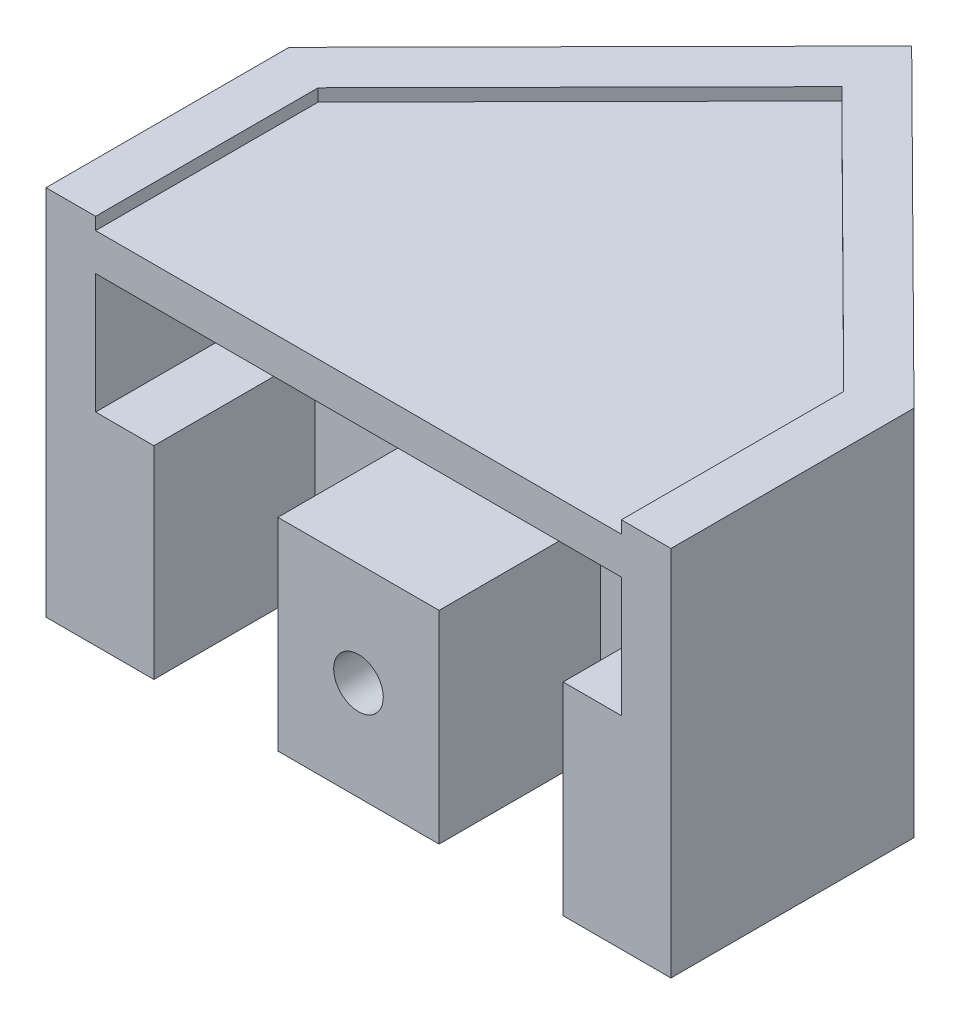
SolidWorks part; units mm, degrees
ref_plane "Plan de face" through (0, 0, 0) normal (0, 0, 1) x (1, 0, 0)
ref_plane "Plan de dessus" through (0, 0, 0) normal (0, 1, 0) x (1, 0, 0)
ref_plane "Plan de droite" through (0, 0, 0) normal (1, 0, 0) x (0, 0, -1)
sketch "Sketch2" plane through (0, 0, 0) normal (0, 0, 1) x (1, 0, 0)
  line L1 (0, 0) -> (-25.2, 0)
  line L2 (0, 0) -> (0, 15)
  line L3 (0, 15) -> (-25.2, 15)
  line L4 (-25.2, 0) -> (-25.2, 15)
  dimension "D1" = 25.2
  dimension "D2" = 15
extrude "Boss-Extrude2" add sketch "Sketch2" along normal blind 2
sketch "Sketch3" plane through (0, 0, 2) normal (0, 0, 1) x (1, 0, 0)
  line L0 (0, 15) -> (-25.2, 15) construction
  line L1 (-25.2, 0) -> (-23.2, 0)
  line L2 (-25.2, 0) -> (-25.2, 15)
  line L3 (-25.2, 15) -> (-23.2, 15)
  line L4 (-23.2, 0) -> (-23.2, 15)
  line L6 (-23.2, 13) -> (0, 13)
  line L7 (-23.2, 13) -> (-23.2, 15)
  line L8 (-23.2, 15) -> (0, 15)
  line L9 (0, 13) -> (0, 15)
  line L10 (0, 0) -> (-2, 0)
  line L11 (0, 0) -> (0, 13)
  line L12 (0, 13) -> (-2, 13)
  line L13 (-2, 0) -> (-2, 13)
  line M4 (0, 0) -> (0, 15)
  line M5 (0, 15) -> (-25.2, 15)
  line M6 (-25.2, 15) -> (-25.2, 0)
  line M7 (-25.2, 0) -> (0, 0)
  dimension "D1" = 2
  dimension "D2" = 2
  dimension "D3" = 2
extrude "Boss-Extrude3" add sketch "Sketch3" along normal blind 7.8 contours L4 M7 M5 M6 | L4 L6 M4 M5 | L13 L6 M7 M4 region at (-24.2, 7.5, 2) region at (-11.6, 14, 2) region at (-1, 6.5, 2)
sketch "Sketch4" plane through (0, 15, 0) normal (0, 1, 0) x (1, 0, 0)
  line L0 (0, 0) -> (-12.6933, 12.5997) construction
  line L1 (-25.2, 0) -> (-12.6933, 12.5997) construction
  line L2 (0, 0) -> (-12.6933, 12.5997)
  line L3 (-12.6933, 12.5997) -> (-25.2, 0)
  line L4 (-25.2, 0) -> (0, 0)
  point P4 (-12.8999, 12.9691)
  point P6 (-12.2, 12.9581)
extrude "Boss-Extrude4" add sketch "Sketch4" against normal through all
sketch "Sketch5" plane through (0, 0, 2) normal (0, 0, 1) x (1, 0, 0)
  line L0 (-23.2, 0) -> (-2, 0) construction
  line L1 (-20.85, 0) -> (-4.35, 0)
  line L2 (-20.85, 0) -> (-20.85, 8.1631)
  line L3 (-20.85, 8.1631) -> (-4.35, 8.1631)
  line L4 (-4.35, 0) -> (-4.35, 8.1631)
  line L5 (-20.1, 6) -> (-20.1, 8.5) construction
  line L7 (-2, 0) -> (-2, 13) construction
  line L8 (-23.2, 0) -> (-2, 0)
  line L9 (-23.2, 0) -> (-23.2, 8.1631)
  line L10 (-23.2, 8.1631) -> (-2, 8.1631)
  line L11 (-2, 0) -> (-2, 8.1631)
  line L12 (-17.6, 6) -> (-17.6, 8.5) construction
  line L13 (-15.85, 0) -> (-9.35, 0)
  line L14 (-15.85, 0) -> (-15.85, 8.1631)
  line L15 (-15.85, 8.1631) -> (-9.35, 8.1631)
  line L16 (-9.35, 0) -> (-9.35, 8.1631)
  line M7 (-23.2, 0) -> (-2, 0)
  line M8 (-2, 0) -> (-2, 13)
  line M10 (-23.2, 13) -> (-23.2, 0)
  dimension "D1" = 16.5
  dimension "D2" = 0.75
  dimension "D3" = 0
  dimension "D4" = 6.5
  dimension "D5" = 1.75
extrude "Boss-Extrude5" add sketch "Sketch5" along normal blind 7.8 contours L8 L16 L10 L14 | L10 L4 M7 M8 | L10 L2 M10 M7 region at (-22.025, 4.0815, 2) region at (-12.6, 4.0815, 2) region at (-3.175, 4.0815, 2)
sketch "Sketch6" plane through (0, 0, 2) normal (0, 0, 1) x (1, 0, 0)
  line L1 (-20.85, 0) -> (-15.85, 0)
  line L2 (-20.85, 0) -> (-20.85, 8.1631)
  line L3 (-20.85, 8.1631) -> (-15.85, 8.1631)
  line L4 (-15.85, 0) -> (-15.85, 8.1631)
  line L5 (-9.35, 0) -> (-4.35, 0)
  line L6 (-9.35, 0) -> (-9.35, 8.1631)
  line L7 (-9.35, 8.1631) -> (-4.35, 8.1631)
  line L8 (-4.35, 0) -> (-4.35, 8.1631)
extrude "Boss-Extrude6" add sketch "Sketch6" along normal blind 1.3
sketch "Sketch8" plane through (0, 15, 0) normal (0, 1, 0) x (1, 0, 0)
  line L6 (-23.2, -7.8) -> (-2, -7.8)
  line L7 (-23.2, -7.8) -> (-23.2, -9.8)
  line L8 (-23.2, -9.8) -> (-2, -9.8)
  line L9 (-2, -7.8) -> (-2, -9.8)
  line L10 (-2, -7.8) -> (-2, -0.8328)
  line L11 (-2, -0.8328) -> (-12.6829, 9.7712)
  line L12 (-12.6829, 9.7712) -> (-23.2, -0.8241)
  line L13 (-23.2, -0.8241) -> (-23.2, -7.8)
  line L14 (-23.2, -7.8) -> (-2, -7.8)
  line L15 (-2, -7.8) -> (-2, -0.8328)
  line L16 (-2, -0.8328) -> (-12.6829, 9.7712)
  line L17 (-12.6829, 9.7712) -> (-23.2, -0.8241)
  line L18 (-23.2, -0.8241) -> (-23.2, -7.8)
  line L19 (-23.2, -7.8) -> (-2, -7.8)
  line M10 (-25.2, -9.8) -> (0, -9.8)
  dimension "D1" = 2
extrude "Cut-Extrude1" cut sketch "Sketch8" against normal blind 0.5 contours L17 L18 L6 L15 L16 | L9 L6 L7 M10 region at (-12.6132, 15, 1.2828) region at (-12.6, 15, 8.8)
sketch "Sketch10" plane through (0, 0, 9.8) normal (0, 0, 1) x (1, 0, 0)
  circle A0 centre (-12.6, 4) radius 1
extrude "Cut-Extrude4" cut sketch "Sketch10" along direction (0, 0, 1) on the side against the normal blind 6
